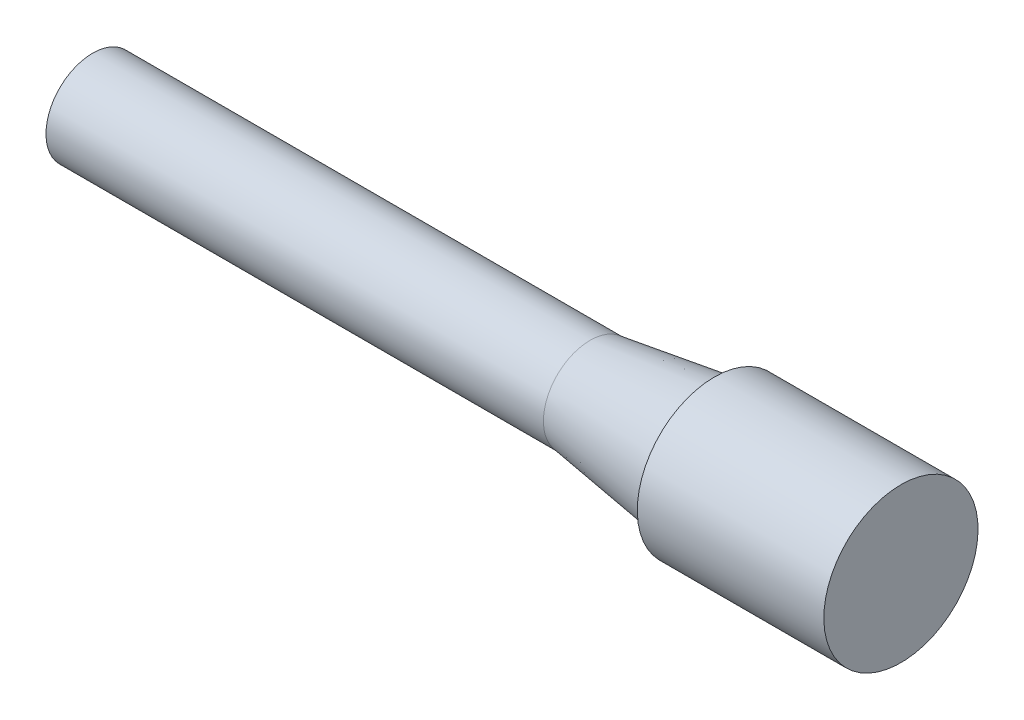
SolidWorks part; units mm, degrees
material "Water"
ref_plane "XY" through (0, 0, 0) normal (0, 0, 1) x (1, 0, 0)
ref_plane "XZ" through (0, 0, 0) normal (0, 1, 0) x (1, 0, 0)
ref_plane "YZ" through (0, 0, 0) normal (1, 0, 0) x (0, 0, -1)
ref_axis "X" through (-88.99, 0, 0) along (1, 0, 0)
ref_axis "Y" through (0, -55, 0) along (0, 1, 0)
ref_axis "Z" through (0, 0, 55) along (0, 0, -1)
sketch "Sketch1" plane through (0, 0, 0) normal (0, 0, 1) x (1, 0, 0)
  line L0 (0, 0) -> (-82.55, 0)
  line L2 (-31.75, 4.7625) -> (-19.05, 6.604)
  line L3 (-19.05, 6.604) -> (-19.05, 7.874)
  line L4 (-19.05, 7.874) -> (0, 7.874)
  line L5 (0, 7.874) -> (0, 0)
  line L6 (-82.55, 0) -> (-82.55, 4.7625)
  line L7 (-82.55, 4.7625) -> (-31.75, 4.7625)
  dimension "D1" = 7.874
  dimension "D2" = 19.05
  dimension "D3" = 12.7
  dimension "D4" = 4.7625
  dimension "D5" = 1.27
  dimension "D6" = 50.8
revolve "Revolve1" add sketch "Sketch1" angle 360 about L0
